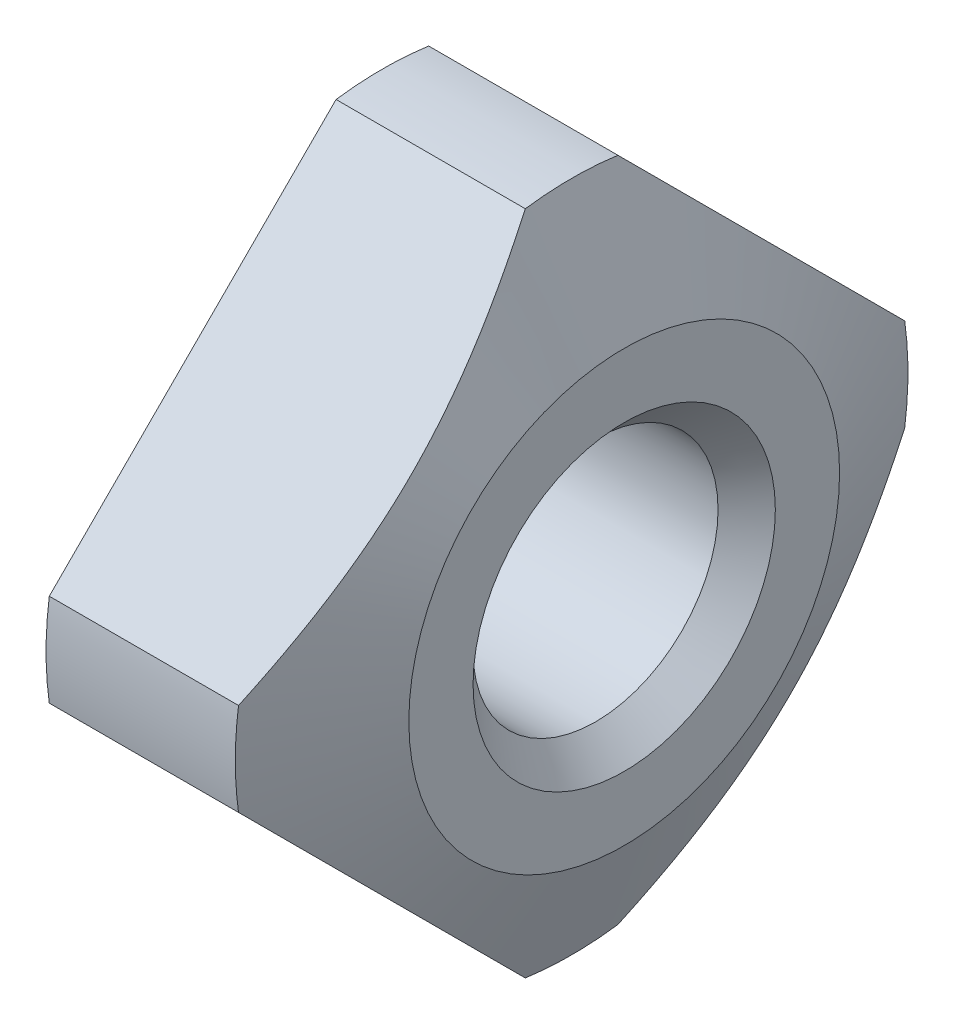
SolidWorks part; units mm, degrees
ref_plane "Front Plane" through (0, 0, 0) normal (0, 0, 1) x (1, 0, 0)
ref_plane "Top Plane" through (0, 0, 0) normal (0, 1, 0) x (1, 0, 0)
ref_plane "Right Plane" through (0, 0, 0) normal (1, 0, 0) x (0, 0, -1)
sketch "Sketch1" plane through (0, 0, 0) normal (0, 0, 1) x (1, 0, 0)
  line L0 (0, 0) -> (0, 4.9497)
  line L1 (0, 4.9497) -> (2.287, 4.9497)
  line L2 (2.287, 4.9497) -> (3.2, 2.85)
  line L3 (3.2, 2.85) -> (3.2, 0)
  line L4 (3.2, 0) -> (0, 0)
  line L5 (3.2, 0) -> (0, 0) construction
revolve "Revolve1" add sketch "Sketch1" angle 360 about L5 reverse direction yes
sketch "Sketch2" plane through (0, 0, 0) normal (1, 0, 0) x (0, 0, -1)
  line L0 (-14, 14) -> (-14, -14)
  line L1 (-14, -14) -> (14, -14)
  line L2 (14, -14) -> (14, 14)
  line L3 (14, 14) -> (-14, 14)
  line L4 (-5.0205, 0) -> (0, -5.0205)
  line L5 (0, -5.0205) -> (5.0205, 0)
  line L6 (5.0205, 0) -> (0, 5.0205)
  line L7 (0, 5.0205) -> (-5.0205, 0)
extrude "Cut-Extrude1" cut sketch "Sketch2" along normal blind 3.2
sketch "Sketch3" plane through (0, 0, 0) normal (0, 0, 1) x (1, 0, 0)
  line L0 (0, 0) -> (0, 2)
  line L1 (0, 2) -> (0.379, 1.621)
  line L2 (0.379, 1.621) -> (2.821, 1.621)
  line L3 (2.821, 1.621) -> (3.2, 2)
  line L4 (3.2, 2) -> (3.2, 0)
  line L5 (3.2, 0) -> (0, 0)
  line L6 (3.2, 0) -> (0, 0) construction
revolve "Cut-Revolve1" cut sketch "Sketch3" angle 360 about L6 reverse direction yes
cosmetic thread "Cosmetic Thread1" parameters "D1"=3.2, "D2"=4
ref_plane "Plane1" through (3.2, 0, 0) normal (1, 0, 0) x (0, 0, -1)
sketch "Sketch4" plane through (0, 0, 0) normal (1, 0, 0) x (0, 0, -1)
  line L0 (-7, 7) -> (-7, -7)
  line L1 (-7, -7) -> (7, -7)
  line L2 (7, -7) -> (7, 7)
  line L3 (7, 7) -> (-7, 7)
  circle A0 centre (0, 0) radius 4.45
extrude "Cut-Extrude2" cut sketch "Sketch4" along normal blind 3.2
ref_plane "IP1 XY" through (0, 0, 0) normal (1, 0, 0) x (0, 0, -1)
ref_plane "IP1 XZ" through (0, 0, 0) normal (0, -1, 0) x (-1, 0, 0)
ref_plane "IP1 YZ" through (0, 0, 0) normal (0, 0, -1) x (-1, 0, 0)
ref_axis "IP1 X" through (0, 0, 80.9) along (0, 0, -1)
ref_axis "IP1 Y" through (0, -50, 0) along (0, 1, 0)
ref_axis "IP1 Z" through (80.9, 0, 0) along (-1, 0, 0)
sketch3d "IP1"
  point P0 (0, 0, 0)
ref_plane "IP2 XY" through (3.2, 0, 0) normal (1, 0, 0) x (0, 0, -1)
ref_plane "IP2 XZ" through (0, 0, 0) normal (0, -1, 0) x (-1, 0, 0)
ref_plane "IP2 YZ" through (0, 0, 0) normal (0, 0, -1) x (-1, 0, 0)
ref_axis "IP2 X" through (3.2, 0, 80.9) along (0, 0, -1)
ref_axis "IP2 Y" through (3.2, -50, 0) along (0, 1, 0)
ref_axis "IP2 Z" through (80.9, 0, 0) along (-1, 0, 0)
sketch3d "IP2"
  point P0 (3.2, 0, 0)
other "Freeze***"
